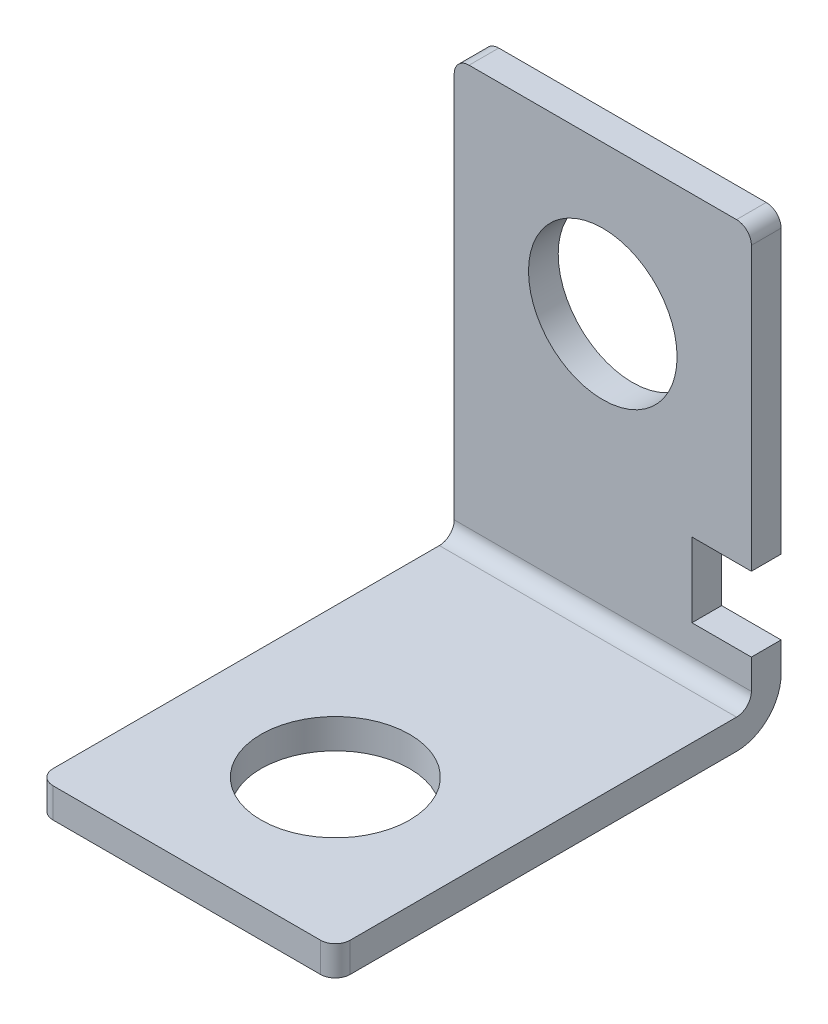
SolidWorks part; units mm, degrees
material "6061 Alloy"
ref_plane "Front Plane" through (0, 0, 0) normal (0, 0, 1) x (1, 0, 0)
ref_plane "Top Plane" through (0, 0, 0) normal (0, 1, 0) x (1, 0, 0)
ref_plane "Right Plane" through (0, 0, 0) normal (1, 0, 0) x (0, 0, -1)
sketch "Sketch1" plane through (0, 0, 0) normal (0, 1, 0) x (1, 0, 0)
  line L0 (0, 0) -> (0, 30)
  line L1 (0, 30) -> (20, 30)
  line L2 (20, 30) -> (20, 0)
  line L3 (20, 0) -> (0, 0)
  line L4 (10, 0) -> (10, 10) construction
  line L5 (10, 10) -> (20, 10) construction
  circle A0 centre (10, 10) radius 5
  point P7 (10, 10.3444)
  dimension "D1" = 30
  dimension "D3" = 10
  dimension "D2" = 20
extrude "Boss-Extrude1" add sketch "Sketch1" along normal blind 2
sketch "Sketch3" plane through (0, 0, -30) normal (0, 0, -1) x (-1, 0, 0)
  line L0 (55, 0) -> (-55, 0) construction
  line L1 (-20, 0) -> (0, 0)
  line L2 (-20, 0) -> (-20, 30)
  line L3 (-20, 30) -> (0, 30)
  line L4 (0, 0) -> (0, 30)
  line L5 (-20, 2) -> (-20, 0) construction
  line L6 (-10, 30) -> (-10, 20) construction
  line L7 (-10, 20) -> (0, 20) construction
  circle A0 centre (-10, 20) radius 5
  point P13 (-10, 19.7285)
  dimension "D1" = 30
  dimension "D3" = 10
  dimension "D2" = 20
extrude "Boss-Extrude2" add sketch "Sketch3" against normal blind 2 contours L2 L1 L4 L3
extrude "Cut-Extrude1" cut sketch "Sketch3<3>" against normal blind 2 contours A0 | A0 region at (10, 20, -30)
sketch "Sketch3<3>" plane through (0, 0, -30) normal (0, 0, -1) x (-1, 0, 0) same geometry as "Sketch3"
sketch "Sketch5" plane through (0, 0, -28) normal (0, 0, 1) x (1, 0, 0)
  line L0 (19.1419, 0) -> (19.1419, 5) construction
  line L1 (55, 0) -> (-55, 0) construction
  line L2 (20, 5) -> (16, 5) construction
  line L3 (20, 2) -> (20, 30) construction
  line L4 (16, 5) -> (16, 10) construction
  line L6 (20, 5) -> (16, 5)
  line L7 (20, 5) -> (20, 10)
  line L8 (20, 10) -> (16, 10)
  line L9 (16, 5) -> (16, 10)
extrude "Cut-Extrude2" cut sketch "Sketch5" against normal blind 2
fillet "Fillet1" radius 1 4 edges at (0, 30, -29) (20, 30, -29) (20, 1, 0) (0, 1, 0)
fillet "Fillet2" radius 1 1 edges at (10, 2, -28)
fillet "Fillet3" radius 3 1 edges at (10, 0, -30)
